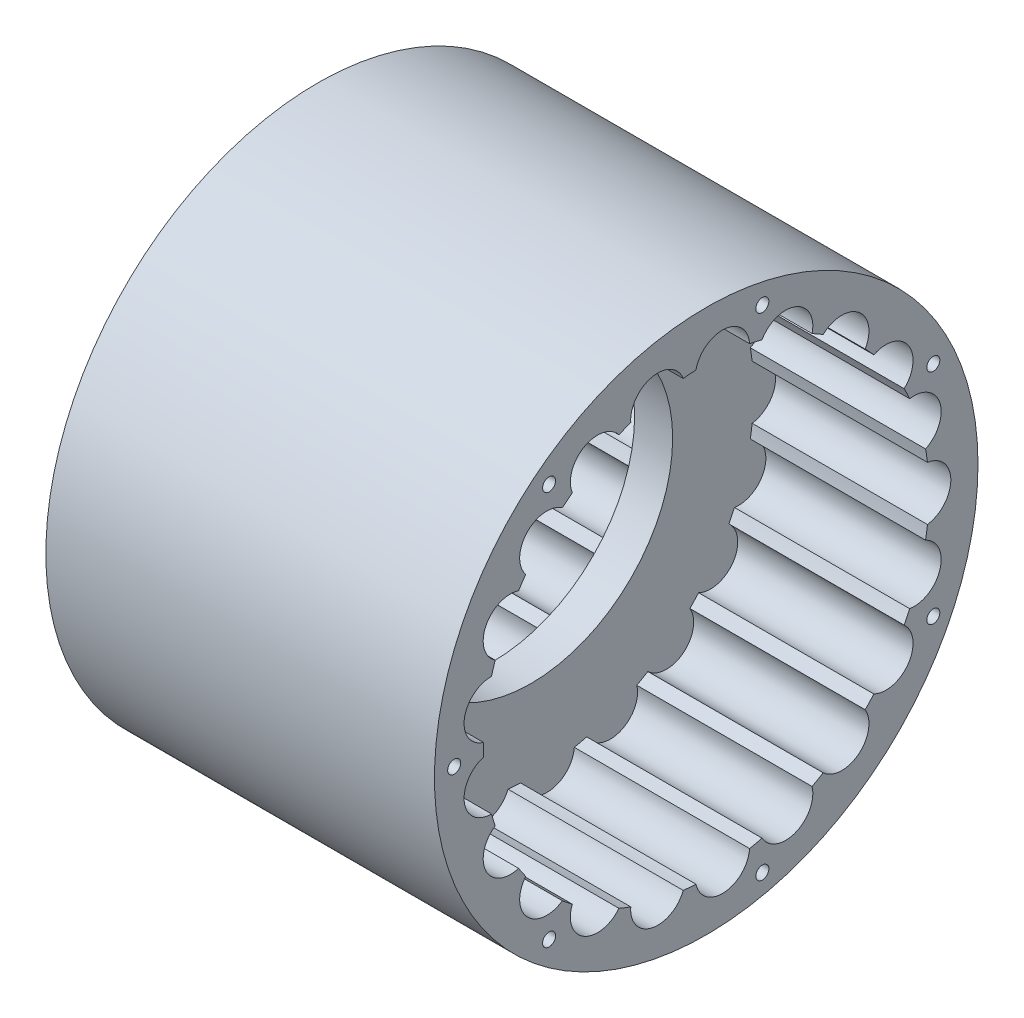
SolidWorks part; units mm, degrees
ref_plane "Ebene vorne" through (0, 0, 0) normal (0, 0, 1) x (1, 0, 0)
ref_plane "Ebene oben" through (0, 0, 0) normal (0, 1, 0) x (1, 0, 0)
ref_plane "Ebene rechts" through (0, 0, 0) normal (1, 0, 0) x (0, 0, -1)
sketch "Skizze2" plane through (0, 0, 0) normal (0, 0, 1) x (1, 0, 0)
  line L0 (0, 0) -> (-33680.1149, 0) construction
  line L1 (0, 26.075) -> (3.5, 26.075)
  line L2 (3.5, 26.075) -> (3.5, 41)
  line L3 (3.5, 41) -> (35.75, 41)
  line L4 (35.75, 41) -> (35.75, 50)
  line L5 (35.75, 50) -> (0, 50)
  line L6 (0, 50) -> (0, 26.075)
  line L7 (0, 0) -> (0, 50000) construction
  dimension "D1" = 52.15
  dimension "D2" = 3.5
  dimension "D3" = 35.75
  dimension "D4" = 100
  dimension "D5" = 82
revolve "Rotation1" add sketch "Skizze2" angle 360 about L0
sketch "Skizze4" plane through (35.75, 0, 0) normal (1, 0, 0) x (0, 0, -1)
  line L0 (0, 0) -> (-50000, 0) construction
  circle A6 centre (0, 0) radius 40 construction
  circle A7 centre (40, 0) radius 5
  circle A8 centre (38.2229, -11.7902) radius 5
  circle A9 centre (33.0496, -22.5328) radius 5
  circle A10 centre (24.9396, -31.2733) radius 5
  circle A11 centre (14.6136, -37.2349) radius 5
  circle A12 centre (2.9892, -39.8882) radius 5
  circle A13 centre (-8.9008, -38.9971) radius 5
  circle A14 centre (-20, -34.641) radius 5
  circle A15 centre (-29.3221, -27.2069) radius 5
  circle A16 centre (-36.0388, -17.3553) radius 5
  circle A17 centre (-39.5532, -5.9617) radius 5
  circle A18 centre (-39.5532, 5.9617) radius 5
  circle A19 centre (-36.0388, 17.3553) radius 5
  circle A20 centre (-29.3221, 27.2069) radius 5
  circle A21 centre (-20, 34.641) radius 5
  circle A22 centre (-8.9008, 38.9971) radius 5
  circle A23 centre (2.9892, 39.8882) radius 5
  circle A24 centre (14.6136, 37.2349) radius 5
  circle A25 centre (24.9396, 31.2733) radius 5
  circle A26 centre (33.0496, 22.5328) radius 5
  circle A27 centre (38.2229, 11.7902) radius 5
  point P49 (0, 0)
  dimension "D2" = 10
  dimension "D3" = 21
extrude "Schnitt-Linear austragen1" cut sketch "Skizze4" against normal up to surface (32.25 mm away) up to face at (3.5, 0, -41)
sketch "Skizze5" plane through (35.75, 0, 0) normal (1, 0, 0) x (0, 0, -1)
  line L0 (0, 0) -> (-50000, 0) construction
  circle A0 centre (-46.3698, 0) radius 1.2
  circle A1 centre (-28.9111, 36.2534) radius 1.2
  circle A2 centre (10.3183, 45.2073) radius 1.2
  circle A3 centre (41.7778, 20.1191) radius 1.2
  circle A4 centre (41.7778, -20.1191) radius 1.2
  circle A5 centre (10.3183, -45.2073) radius 1.2
  circle A6 centre (-28.9111, -36.2534) radius 1.2
  point P20 (0, 0)
  dimension "D1" = 2.4
extrude "Schnitt-Linear austragen2" cut sketch "Skizze5" against normal blind 13
mirror "Spiegeln1" about plane through (0, 0, 0) normal (1, 0, 0) of "Schnitt-Linear austragen2", "Schnitt-Linear austragen1", "Rotation1"
